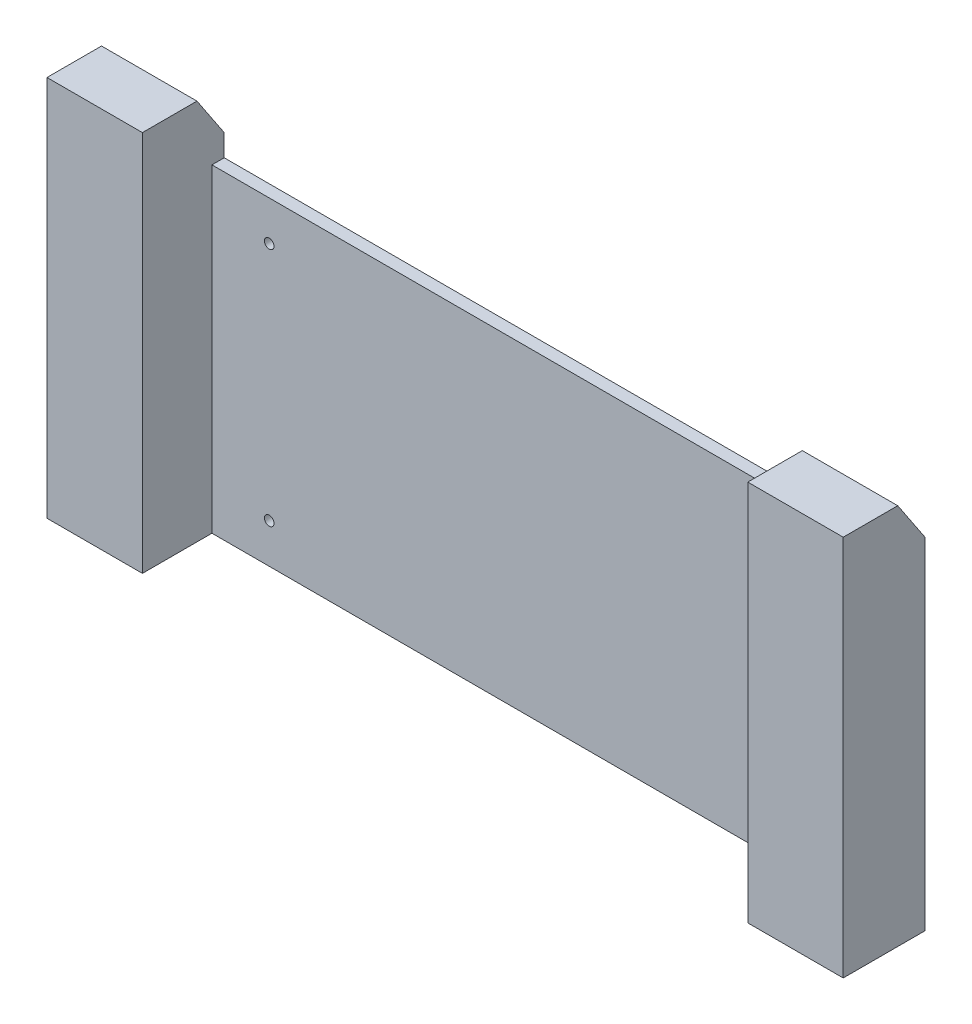
SolidWorks part; units mm, degrees
material "ABS"
ref_plane "Front Plane" through (0, 0, 0) normal (0, 0, 1) x (1, 0, 0)
ref_plane "Top Plane" through (0, 0, 0) normal (0, 1, 0) x (1, 0, 0)
ref_plane "Right Plane" through (0, 0, 0) normal (1, 0, 0) x (0, 0, -1)
sketch "Sketch1" plane through (0, 0, 0) normal (0, 0, 1) x (1, 0, 0)
  line L0 (0, 0) -> (0, 166.746) construction
  line L1 (146, -58.5) -> (-146, -58.5)
  line L2 (146, -58.5) -> (146, 58.5)
  line L3 (146, 58.5) -> (-146, 58.5)
  line L4 (-146, -58.5) -> (-146, 58.5)
  line L5 (146, -58.5) -> (-146, 58.5) construction
  line L6 (146, 58.5) -> (-146, -58.5) construction
  line L7 (0, 0) -> (-259.0657, 0) construction
  circle A0 centre (-90, 44) radius 1.75
  point P0 (0, 0)
  dimension "D5" = 3.5
  dimension "D1" = 292
  dimension "D2" = 117
  dimension "D3" = 44
  dimension "D4" = 90
extrude "Boss-Extrude1" add sketch "Sketch1" along normal blind 4.5 contours L4 L1 L2 L3 A0 | A0 region at (0.0254, -0.0124, 0) region at (-90, 44, 0)
extrude "Cut-Extrude1" cut sketch "Sketch1<3>" along normal up to next contours A0
sketch "Sketch1<3>" plane through (0, 0, 0) normal (0, 0, 1) x (1, 0, 0) same geometry as "Sketch1"
mirror "Mirror2" about plane through (0, 0, 0) normal (0, 1, 0) of "Cut-Extrude1"
mirror "Mirror3" about plane through (0, 0, 0) normal (1, 0, 0) of "Mirror2"
sketch "Sketch2" plane through (0, 0, 0) normal (0, 0, -1) x (-1, 0, 0)
  line L1 (-146, -58.5) -> (-111, -58.5)
  line L2 (-146, -58.5) -> (-146, 81.5)
  line L3 (-146, 81.5) -> (-111, 81.5)
  line L4 (-111, -58.5) -> (-111, 81.5)
  dimension "D1" = 140
  dimension "D2" = 35
extrude "Boss-Extrude2" add sketch "Sketch2" against normal blind 30
chamfer "Chamfer1" distance 10 distance2 15 1 edges at (128.5, 81.5, 0) first distance on face at (128.5, 81.5, 15)
mirror "Mirror5" about plane through (0, 0, 0) normal (1, 0, 0) of "Boss-Extrude2"
chamfer "Chamfer2" distance 15 distance2 10 1 edges at (-128.5, 81.5, 0) first distance on face at (0, 37, 0)
